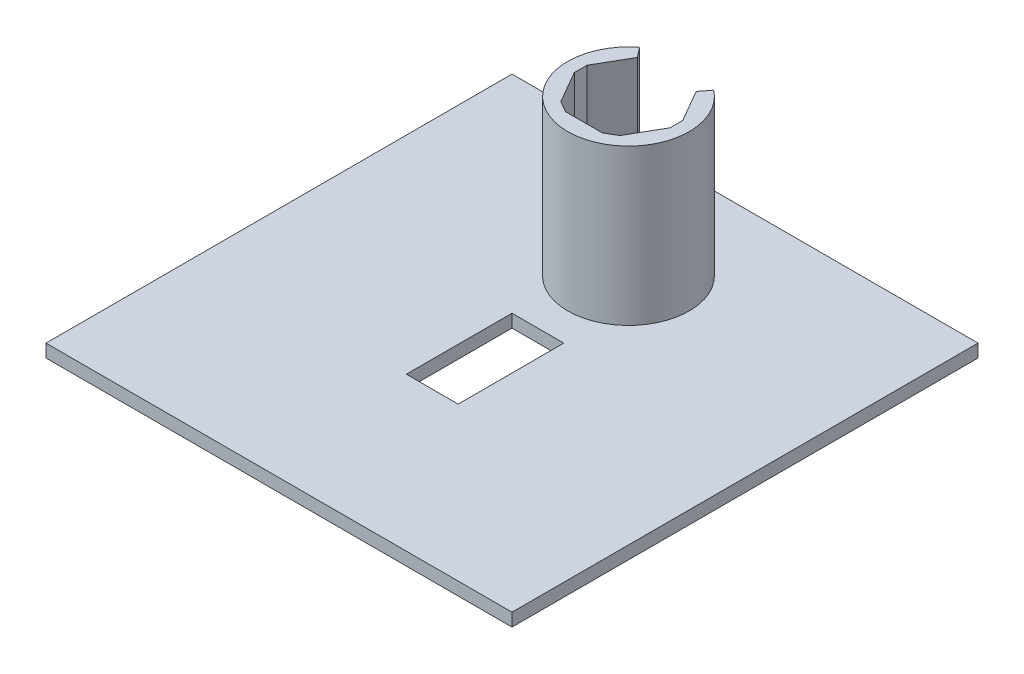
SolidWorks part; units mm, degrees
ref_plane "Front Plane" through (0, 0, 0) normal (0, 0, 1) x (1, 0, 0)
ref_plane "Top Plane" through (0, 0, 0) normal (0, 1, 0) x (1, 0, 0)
ref_plane "Right Plane" through (0, 0, 0) normal (1, 0, 0) x (0, 0, -1)
sketch "Sketch2" plane through (0, 0, 0) normal (0, 1, 0) x (1, 0, 0)
  line L1 (-90, -90) -> (90, -90)
  line L2 (-90, -90) -> (-90, 90)
  line L3 (-90, 90) -> (90, 90)
  line L4 (90, -90) -> (90, 90)
  line L5 (-90, -90) -> (90, 90) construction
  line L6 (-90, 90) -> (90, -90) construction
  point P0 (0, 0)
  dimension "D1" = 180
extrude "Boss-Extrude1" add sketch "Sketch2" along normal blind 5
sketch "Sketch3" plane through (0, 5, 0) normal (0, 1, 0) x (1, 0, 0)
  line L0 (-11.3742, 30.2347) -> (-14.3254, 26.4037)
  line L1 (11.3742, 30.2347) -> (14.3254, 26.4037)
  line L2 (90, 90) -> (-90, 90) construction
  line L3 (-11.3742, 59.7653) -> (-14.3254, 63.5963)
  line L4 (11.3742, 59.7653) -> (14.3254, 63.5963)
  line L5 (7.1, 62.233) -> (-7.1, 62.233)
  line L6 (-11.3742, 59.7653) -> (-18.4742, 47.4677)
  line L14 (-18.4742, 42.5323) -> (-11.3742, 30.2347)
  line L15 (-7.1, 27.767) -> (7.1, 27.767)
  line L16 (11.3742, 30.2347) -> (18.4742, 42.5323)
  line L17 (18.4742, 47.4677) -> (11.3742, 59.7653)
  line L18 (-7.1, 62.233) -> (-11.3742, 59.7653)
  line L19 (-18.4742, 47.4677) -> (-18.4742, 42.5323)
  line L20 (-11.3742, 30.2347) -> (-7.1, 27.767)
  line L21 (7.1, 27.767) -> (11.3742, 30.2347)
  line L22 (18.4742, 42.5323) -> (18.4742, 47.4677)
  line L23 (11.3742, 59.7653) -> (7.1, 62.233)
  circle A0 centre (0, 45) radius 17.233 construction
  circle A1 centre (0, 45) radius 18.4742 construction
  circle A2 centre (0, 45) radius 23.4742
  point P1 (14.3254, 63.5963)
  point P4 (0, 45)
  point P7 (-14.3254, 63.5963)
  point P8 (0, 14.65)
  point P13 (0, -14.65)
  point P22 (0, 0)
  point P24 (-7.4159, 13.8948)
  point P36 (0, 45)
  dimension "D2" = 5
  dimension "D1" = 4.9354
  dimension "D3" = 45
  dimension "D9" = 14.2
extrude "Boss-Extrude2" add sketch "Sketch3" along normal blind 60 contours L3 A2 L0 L14 L19 L6 | L1 A2 L4 L17 L22 L16 | L0 A2 L1 L21 L15 L20 region at (0, 5, -25.5326) region at (-13.1596, 5, -28.5579) region at (13.1596, 5, -28.5579)
sketch "Sketch4" plane through (0, 5, 0) normal (0, 1, 0) x (1, 0, 0)
  line L0 (90, 90) -> (-90, 90) construction
  line L1 (-10, 10) -> (10, 10)
  line L2 (-10, 10) -> (-10, -30.8)
  line L3 (-10, -30.8) -> (10, -30.8)
  line L4 (10, 10) -> (10, -30.8)
  line L5 (-10, 10) -> (10, -30.8) construction
  line L6 (-10, -30.8) -> (10, 10) construction
  circle A0 centre (0, 0) radius 2.25
  point P0 (0, -10.4)
  point P7 (0, 0)
  point P9 (0, 0)
  point P12 (0, 0)
  dimension "D3" = 4.5
  dimension "D1" = 40.8
  dimension "D2" = 20
  dimension "D4" = 10
  dimension "D5" = 10
  dimension "D6" = 90
extrude "Cut-Extrude1" cut sketch "Sketch4" against normal up to surface (5 mm away) contours A0 | L4 L1 L2 L3 A0 region at (0, 5, 10.6067) region at (0, 5, 0) up to face at (0, 0, 0)
